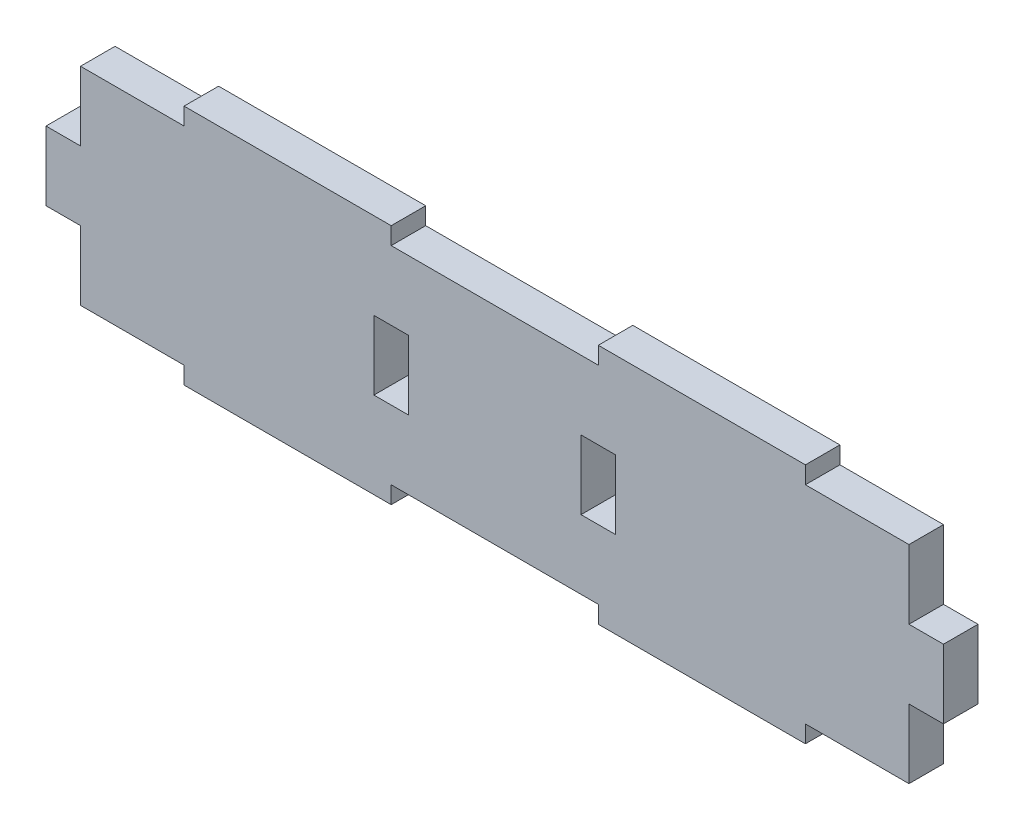
SolidWorks part; units mm, degrees
material "7050-T73510"
ref_plane "Front Plane" through (0, 0, 0) normal (0, 0, 1) x (1, 0, 0)
ref_plane "Top Plane" through (0, 0, 0) normal (0, 1, 0) x (1, 0, 0)
ref_plane "Right Plane" through (0, 0, 0) normal (1, 0, 0) x (0, 0, -1)
sketch "Sketch1" plane through (0, 0, 0) normal (0, 0, 1) x (1, 0, 0)
  line L1 (-165.1, -38.1) -> (165.1, -38.1)
  line L2 (-165.1, -38.1) -> (-165.1, 38.1)
  line L3 (-165.1, 38.1) -> (165.1, 38.1)
  line L4 (165.1, -38.1) -> (165.1, 38.1)
  line L5 (-165.1, -38.1) -> (165.1, 38.1) construction
  line L6 (-165.1, 38.1) -> (165.1, -38.1) construction
  point P0 (0, 0)
  dimension "D1" = 330.2
  dimension "D2" = 76.2
extrude "Boss-Extrude1" add sketch "Sketch1" along normal blind 12.7 contours L1 L3 region at (0, 0, 0)
sketch "Sketch2" plane through (0, 0, 12.7) normal (0, 0, 1) x (1, 0, 0)
  line L0 (-165.1, -38.1) -> (165.1, -38.1) construction
  line L1 (-38.1, -38.1) -> (-114.3, -38.1)
  line L2 (-38.1, -38.1) -> (-38.1, -44.45)
  line L3 (-38.1, -44.45) -> (-114.3, -44.45)
  line L4 (-114.3, -38.1) -> (-114.3, -44.45)
  line L5 (0, -55) -> (0, 55) construction
  line L6 (38.1, -44.45) -> (114.3, -44.45)
  line L7 (114.3, -38.1) -> (114.3, -44.45)
  line L8 (38.1, -38.1) -> (114.3, -38.1)
  line L9 (38.1, -38.1) -> (38.1, -44.45)
  line L10 (55, 0) -> (-55, 0) construction
  line L11 (38.1, 38.1) -> (38.1, 44.45)
  line L12 (38.1, 38.1) -> (114.3, 38.1)
  line L13 (114.3, 38.1) -> (114.3, 44.45)
  line L14 (38.1, 44.45) -> (114.3, 44.45)
  line L15 (-38.1, 44.45) -> (-114.3, 44.45)
  line L16 (-114.3, 38.1) -> (-114.3, 44.45)
  line L17 (-38.1, 38.1) -> (-114.3, 38.1)
  line L18 (-38.1, 38.1) -> (-38.1, 44.45)
  point P12 (-38.1, -41.275)
  dimension "D1" = 76.2
  dimension "D2" = 6.35
  dimension "D3" = 76.2
extrude "Boss-Extrude2" add sketch "Sketch2" against normal blind 12.7
sketch "Sketch3" plane through (0, 0, 12.7) normal (0, 0, 1) x (1, 0, 0)
  line L0 (6.985, 0) -> (-6.985, 0) construction
  line L1 (-165.1, -38.1) -> (-152.4, -38.1)
  line L2 (-165.1, -38.1) -> (-165.1, -12.7)
  line L3 (-165.1, -12.7) -> (-152.4, -12.7)
  line L4 (-152.4, -38.1) -> (-152.4, -12.7)
  line L6 (-165.1, 12.7) -> (-152.4, 12.7)
  line L7 (-152.4, 38.1) -> (-152.4, 12.7)
  line L8 (-165.1, 38.1) -> (-152.4, 38.1)
  line L9 (-165.1, 38.1) -> (-165.1, 12.7)
  line L10 (0, -6.985) -> (0, 6.985) construction
  line L11 (165.1, 38.1) -> (165.1, 12.7)
  line L12 (165.1, 38.1) -> (152.4, 38.1)
  line L13 (152.4, 38.1) -> (152.4, 12.7)
  line L14 (165.1, 12.7) -> (152.4, 12.7)
  line L15 (165.1, -12.7) -> (152.4, -12.7)
  line L16 (152.4, -38.1) -> (152.4, -12.7)
  line L17 (165.1, -38.1) -> (152.4, -38.1)
  line L18 (165.1, -38.1) -> (165.1, -12.7)
  line L19 (31.75, 12.7) -> (44.45, 12.7)
  line L20 (31.75, 12.7) -> (31.75, -12.7)
  line L21 (31.75, -12.7) -> (44.45, -12.7)
  line L22 (44.45, 12.7) -> (44.45, -12.7)
  line L23 (-38.1, -38.1) -> (38.1, -38.1) construction
  line L24 (-31.75, -12.7) -> (-44.45, -12.7)
  line L25 (-44.45, 12.7) -> (-44.45, -12.7)
  line L26 (-31.75, 12.7) -> (-44.45, 12.7)
  line L27 (-31.75, 12.7) -> (-31.75, -12.7)
  line L28 (-38.1, 38.1) -> (38.1, 38.1) construction
  dimension "D1" = 25.4
  dimension "D2" = 12.7
  dimension "D3" = 63.5
  dimension "D4" = 12.7
  dimension "D5" = 25.4
  dimension "D6" = 25.4
extrude "Cut-Extrude1" cut sketch "Sketch3" against normal through all
